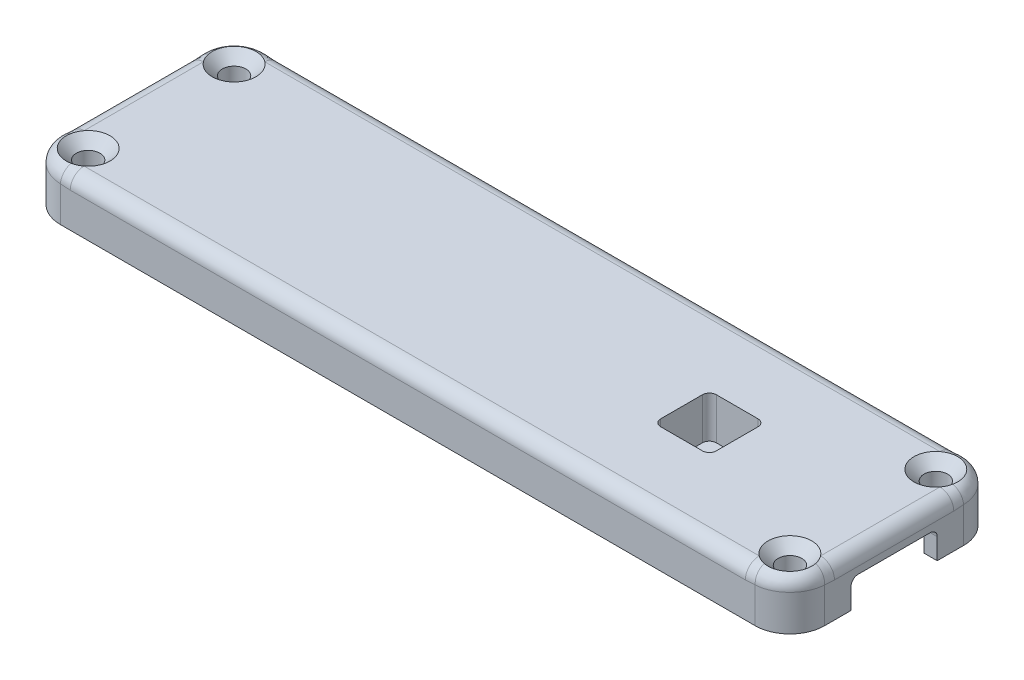
SolidWorks part; units mm, degrees
ref_plane "Front" through (0, 0, 0) normal (0, 0, 1) x (1, 0, 0)
ref_plane "Top" through (0, 0, 0) normal (0, 1, 0) x (1, 0, 0)
ref_plane "Right" through (0, 0, 0) normal (1, 0, 0) x (0, 0, -1)
sketch "Sketch1" plane through (0, 0, 0) normal (0, 1, 0) x (1, 0, 0)
  line L1 (-54.418, 80.1422) -> (55.582, 80.1422)
  line L2 (-54.418, 80.1422) -> (-54.418, 50.1422)
  line L3 (-54.418, 50.1422) -> (55.582, 50.1422)
  line L4 (55.582, 80.1422) -> (55.582, 50.1422)
  dimension "D1" = 30
  dimension "D2" = 110
extrude "Boss-Extrude1" add sketch "Sketch1" along normal blind 5
shell "Shell1" thickness 4 removed face at (0.582, 0, -65.1422)
sketch "Sketch3" plane through (0, 0, 0) normal (0, -1, 0) x (1, 0, 0)
  line L0 (-52.518, -52.0422) -> (-52.518, -78.2422)
  line L1 (-52.518, -78.2422) -> (53.682, -78.2422)
  line L2 (53.682, -78.2422) -> (53.682, -52.0422)
  line L3 (53.682, -52.0422) -> (-52.518, -52.0422)
  line L4 (-54.418, -50.1422) -> (-54.418, -80.1422)
  line L5 (-54.418, -80.1422) -> (55.582, -80.1422)
  line L6 (55.582, -80.1422) -> (55.582, -50.1422)
  line L7 (55.582, -50.1422) -> (-54.418, -50.1422)
  line L8 (-54.418, -50.1422) -> (-54.418, -80.1422)
  line L9 (-54.418, -80.1422) -> (55.582, -80.1422)
  line L10 (55.582, -80.1422) -> (55.582, -50.1422)
  line L11 (55.582, -50.1422) -> (-54.418, -50.1422)
  dimension "D1" = 0
  dimension "D2" = 1.9
extrude "Boss-Extrude2" add sketch "Sketch3" along normal blind 2
hole_wizard "CSK for M3 Countersunk Flat Head Screw2" positions "Sketch7" profile "Sketch5" countersink size "M3" standard "ISO" end condition through all
sketch "Sketch7" plane through (0, 5, 0) normal (0, 1, 0) x (1, 0, 0)
  point P0 (-49.918, 75.6422)
  point P3 (-49.918, 54.6422)
  point P6 (51.082, 75.6422)
  point P9 (51.082, 54.6422)
sketch "Sketch5" plane through (-49.918, 5, -75.6422) normal (1, 0, 0) x (0, 0, 1)
  line L0 (0, 0) -> (0, 7)
  line L1 (0, 7) -> (1.7, 7)
  line L2 (1.7, 7) -> (1.7, 1.45)
  line L3 (1.7, 1.45) -> (3.15, 0)
  line L5 (3.15, 0) -> (0, 0)
  line L6 (-1.7, 1.45) -> (-3.15, 0) construction
  line L11 (0, -6.35) -> (0, 107.95) construction
  dimension "Thru Hole Dia." = 3.4
  dimension "Thru Hole Depth" = 7
  dimension "Near C'Sink Dia." = 6.3
  dimension "Near C'Sink Angle" = 90
fillet "Fillet1" radius 5 4 edges at (55.582, 1.5, -50.1422) (55.582, 1.5, -80.1422) (-54.418, 1.5, -80.1422) (-54.418, 1.5, -50.1422)
fillet "Fillet3" radius 2 4 edges at (0.582, 5, -80.1422) (55.582, 5, -65.1422) (0.582, 5, -50.1422) (-54.418, 5, -65.1422)
sketch "Sketch8" plane through (0, -2, 0) normal (0, -1, 0) x (1, 0, 0)
  line L0 (48.482, -69.6422) -> (60.0944, -69.6422) construction
  line L1 (48.482, -69.6422) -> (48.482, -60.6422) construction
  line L2 (48.482, -60.6422) -> (60.0944, -60.6422) construction
  line L3 (60.0944, -69.6422) -> (60.0944, -60.6422) construction
  line L4 (48.482, -69.6422) -> (60.0944, -69.6422)
  line L5 (48.482, -69.6422) -> (48.482, -60.6422)
  line L6 (48.482, -60.6422) -> (60.0944, -60.6422)
  line L7 (60.0944, -69.6422) -> (60.0944, -60.6422)
extrude "Cut-Extrude1" cut sketch "Sketch8" against normal blind 2
sketch "Sketch9" plane through (0, -2, 0) normal (0, -1, 0) x (1, 0, 0)
  line L0 (53.477, -71.3375) -> (55.582, -71.3375) construction
  line L1 (55.582, -58.947) -> (55.582, -71.3375) construction
  line L2 (53.477, -58.947) -> (55.582, -58.947) construction
  line L3 (53.477, -58.947) -> (53.477, -71.3375) construction
  line L4 (53.477, -71.3375) -> (55.582, -71.3375)
  line L5 (55.582, -58.947) -> (55.582, -71.3375)
  line L6 (53.477, -58.947) -> (55.582, -58.947)
  line L7 (53.477, -58.947) -> (53.477, -71.3375)
extrude "Cut-Extrude2" cut sketch "Sketch9" against normal blind 4
fillet "Fillet4" radius 1 2 edges at (54.5295, 2, -71.3375) (54.5295, 2, -58.947)
sketch "Sketch10" plane through (0, 1, 0) normal (0, -1, 0) x (1, 0, 0)
  line L0 (-68.8598, -65.1422) -> (69.4884, -65.1422) construction
  line L1 (24.989, -70.1422) -> (32.989, -70.1422)
  line L2 (23.989, -69.1422) -> (23.989, -61.1422)
  line L3 (24.989, -60.1422) -> (32.989, -60.1422)
  line L4 (33.989, -69.1422) -> (33.989, -61.1422)
  line L5 (51.582, -56.267) -> (51.582, -74.0174) construction
  line L6 (-48.2932, -54.1422) -> (49.4572, -54.1422) construction
  line L8 (49.4572, -76.1422) -> (-48.2932, -76.1422) construction
  arc A0 (32.989, -60.1422) -> (33.989, -61.1422) centre (32.989, -61.1422) cw
  arc A1 (23.989, -61.1422) -> (24.989, -60.1422) centre (24.989, -61.1422) cw
  arc A2 (32.989, -70.1422) -> (33.989, -69.1422) centre (32.989, -69.1422) ccw
  arc A3 (24.989, -70.1422) -> (23.989, -69.1422) centre (24.989, -69.1422) cw
  point P10 (23.989, -60.1422)
  point P13 (33.989, -70.1422)
  point P16 (23.989, -70.1422)
  point P23 (8.7854, -72.4726)
  dimension "D4" = 1
  dimension "D1" = 10
  dimension "D2" = 10
  dimension "D3" = 5
  dimension "D5" = 17.593
  dimension "D6" = 6
  dimension "D7" = 6
extrude "Boss-Extrude3" add sketch "Sketch10" along normal blind 3
sketch "Sketch11" plane through (0, 5, 0) normal (0, 1, 0) x (1, 0, 0)
  line L0 (49.1656, 78.1422) -> (-48.0016, 78.1422) construction
  line L1 (-48.0016, 52.1422) -> (49.1656, 52.1422) construction
  line L5 (23.989, 69.1422) -> (23.989, 61.1422) construction
  line L8 (28.5546, 69.1422) -> (28.5546, 61.1422) construction
  line L9 (24.5546, 65.1422) -> (32.5546, 65.1422) construction
  line L10 (25.989, 69.1422) -> (31.989, 69.1422)
  line L11 (32.989, 68.1422) -> (32.989, 62.1422)
  line L12 (25.989, 61.1422) -> (31.989, 61.1422)
  line L13 (24.989, 68.1422) -> (24.989, 62.1422)
  arc A4 (31.989, 69.1422) -> (32.989, 68.1422) centre (31.989, 68.1422) cw
  arc A5 (32.989, 62.1422) -> (31.989, 61.1422) centre (31.989, 62.1422) cw
  arc A6 (25.989, 61.1422) -> (24.989, 62.1422) centre (25.989, 62.1422) cw
  arc A7 (25.989, 69.1422) -> (24.989, 68.1422) centre (25.989, 68.1422) ccw
  point P24 (9.9265, 57.7257)
  dimension "D1" = 1
  dimension "D2" = 1
  dimension "D3" = 8
  dimension "D4" = 9
  dimension "D5" = 9
extrude "Cut-Extrude3" cut sketch "Sketch11" against normal blind 6
sketch "Sketch12" plane through (0, -1, 0) normal (0, 1, 0) x (1, 0, 0)
  line L0 (28.989, 69.1422) -> (28.989, 61.1422) construction
  line L1 (31.989, 69.1422) -> (25.989, 69.1422) construction
  line L2 (25.989, 61.1422) -> (31.989, 61.1422) construction
  line L3 (24.989, 65.1422) -> (32.989, 65.1422) construction
  line L4 (24.989, 68.1422) -> (24.989, 62.1422) construction
  line L5 (-68.8598, 65.1422) -> (69.4884, 65.1422) construction
  line L6 (32.989, 62.1422) -> (32.989, 68.1422) construction
  circle A0 centre (28.989, 65.1422) radius 1.5
  dimension "D1" = 3
extrude "Cut-Extrude4" cut sketch "Sketch12" against normal up to surface (1 mm away) up to face at (28.989, -2, -65.1422)
